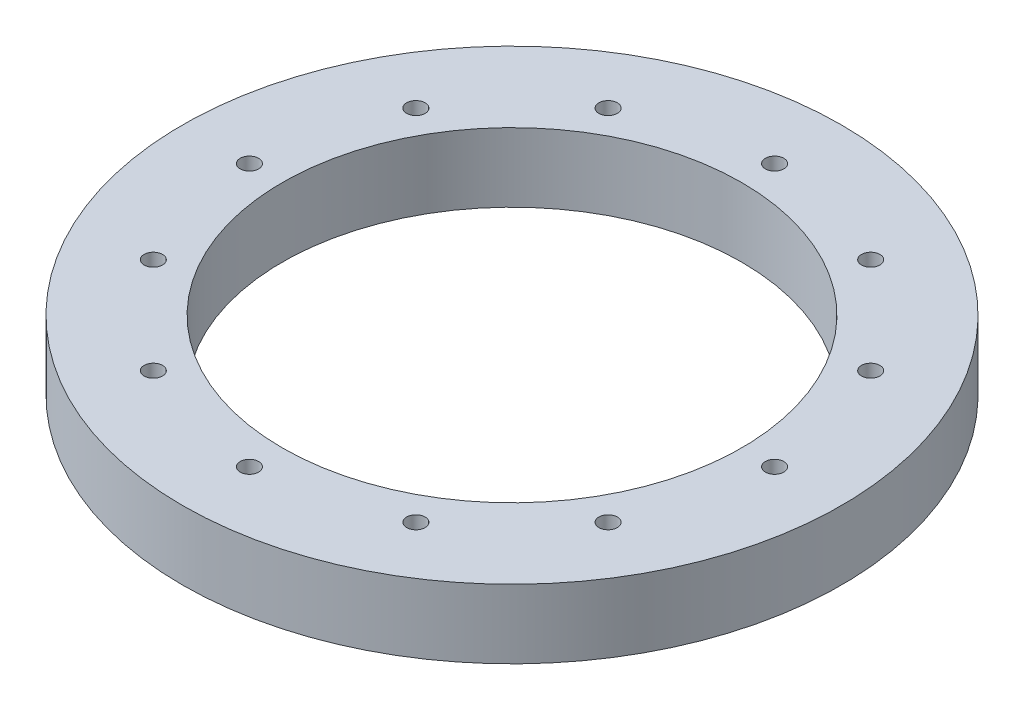
SolidWorks part; units mm, degrees
ref_plane "Front Plane" through (0, 0, 0) normal (0, 0, 1) x (1, 0, 0)
ref_plane "Top Plane" through (0, 0, 0) normal (0, 1, 0) x (1, 0, 0)
ref_plane "Right Plane" through (0, 0, 0) normal (1, 0, 0) x (0, 0, -1)
sketch "Sketch1" plane through (0, 0, 0) normal (0, 1, 0) x (1, 0, 0)
  circle A0 centre (0, 0) radius 101.6 construction
  circle A1 centre (0, 0) radius 127.508
  circle A2 centre (0, 0) radius 88.9
  circle A3 centre (0, 101.6) radius 3.5687
  circle A4 centre (50.8, 87.9882) radius 3.5687
  circle A5 centre (87.9882, 50.8) radius 3.5687
  circle A6 centre (101.6, 0) radius 3.5687
  circle A7 centre (87.9882, -50.8) radius 3.5687
  circle A8 centre (50.8, -87.9882) radius 3.5687
  circle A9 centre (0, -101.6) radius 3.5687
  circle A10 centre (-50.8, -87.9882) radius 3.5687
  circle A11 centre (-87.9882, -50.8) radius 3.5687
  circle A12 centre (-101.6, 0) radius 3.5687
  circle A13 centre (-87.9882, 50.8) radius 3.5687
  circle A14 centre (-50.8, 87.9882) radius 3.5687
  point P31 (0, 0)
  dimension "D1" = 203.2
  dimension "D2" = 255.016
  dimension "D3" = 177.8
  dimension "D4" = 7.1374
  dimension "D5" = 12
extrude "Boss-Extrude1" add sketch "Sketch1" along normal blind 26.67
equation "\"A\"= 10.04in"
equation "\"B\"= 7in"
equation "\"C\"= 5.93in"
equation "\"D\"= .56in"
equation "\"E\"= 5.39in"
equation "\"F\"= 1.03in"
equation "\"D2@Sketch1\"=\"A\""
equation "\"D3@Sketch1\"=\"B\""
equation "\"BC\"=203.2"
equation "\"D1@Sketch1\"=\"BC\""
equation "\"diam_mount_hole\"=7.1374"
equation "\"D4@Sketch1\"=\"diam_mount_hole\""
equation "\"thick\"= 2.1in / 2"
equation "\"D1@Boss-Extrude1\"=\"thick\""
